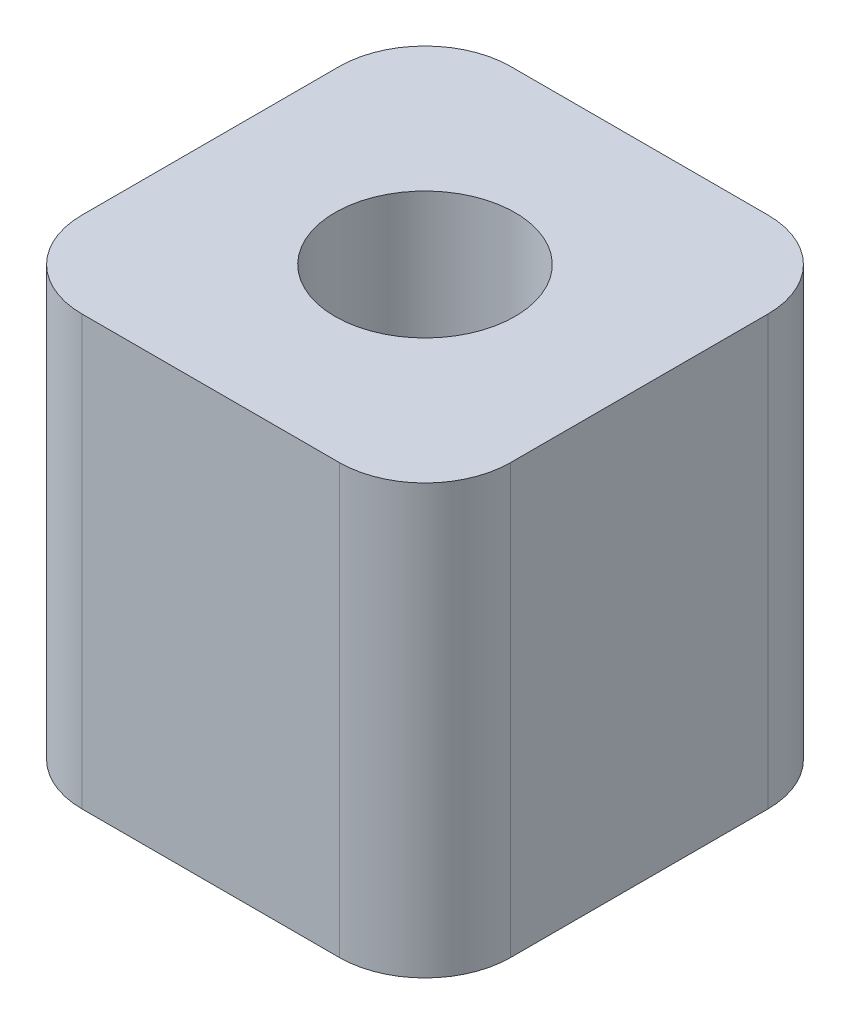
SolidWorks part; units mm, degrees
ref_plane "Front" through (0, 0, 0) normal (0, 0, 1) x (1, 0, 0)
ref_plane "Top" through (0, 0, 0) normal (0, 1, 0) x (1, 0, 0)
ref_plane "Right" through (0, 0, 0) normal (1, 0, 0) x (0, 0, -1)
sketch "Sketch1" plane through (0, 0, 0) normal (0, 1, 0) x (1, 0, 0)
  line L1 (-5, -5) -> (5, -5)
  line L2 (-5, -5) -> (-5, 5)
  line L3 (-5, 5) -> (5, 5)
  line L4 (5, -5) -> (5, 5)
  line L5 (-5, -5) -> (5, 5) construction
  line L6 (-5, 5) -> (5, -5) construction
  circle A0 centre (0, 0) radius 2.1
  point P0 (0, 0)
  dimension "D3" = 4.2
  dimension "D1" = 10
  dimension "D2" = 10
extrude "Boss-Extrude1" add sketch "Sketch1" along normal blind 10
fillet "Fillet1" radius 2 4 edges at (-5, 5, 5) (-5, 5, -5) (5, 5, -5) (5, 5, 5)
equation "\"D2@Sketch1\"=\"D1@Sketch1\""
